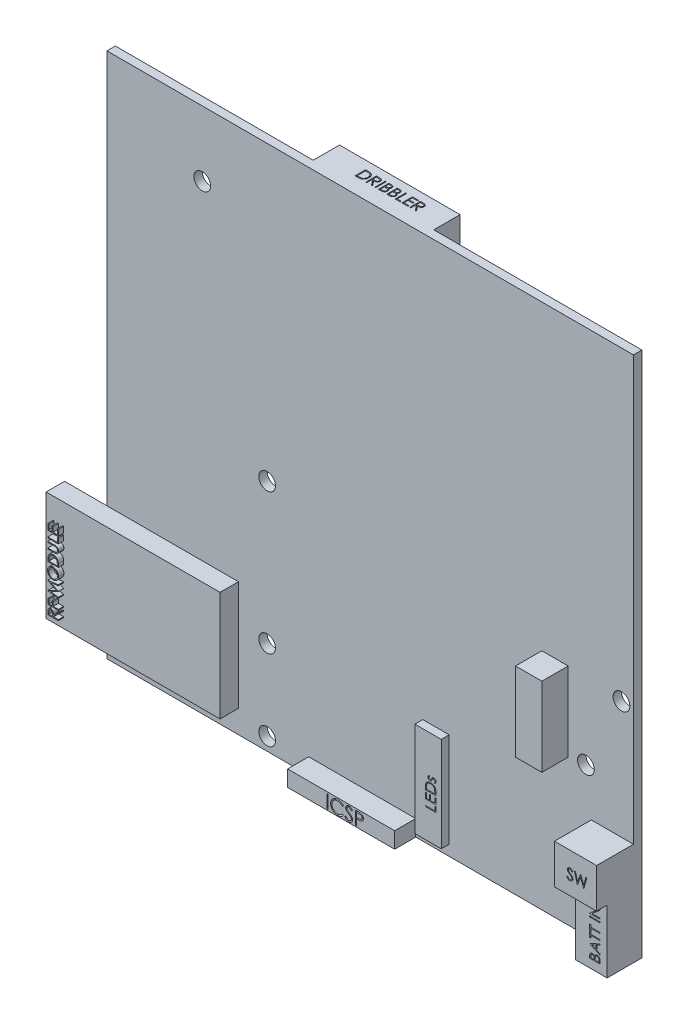
SolidWorks part; units mm, degrees
ref_plane "Front Plane" through (0, 0, 0) normal (0, 0, 1) x (1, 0, 0)
ref_plane "Top Plane" through (0, 0, 0) normal (0, 1, 0) x (1, 0, 0)
ref_plane "Right Plane" through (0, 0, 0) normal (1, 0, 0) x (0, 0, -1)
sketch "Sketch1" plane through (0, 0, 0) normal (0, 0, 1) x (1, 0, 0)
  line L1 (-25.0277, 9.5656) -> (74.9723, 9.5656)
  line L2 (-25.0277, 9.5656) -> (-25.0277, -90.4344)
  line L3 (-25.0277, -90.4344) -> (74.9723, -90.4344)
  line L4 (74.9723, 9.5656) -> (74.9723, -90.4344)
  dimension "D1" = 100
  dimension "D2" = 100
extrude "Boss-Extrude1" add sketch "Sketch1" along normal blind 1.6
sketch "Sketch2" plane through (0, 0, 1.6) normal (0, 0, 1) x (1, 0, 0)
  line L0 (-25.0277, -90.4344) -> (74.9723, -90.4344) construction
  line L1 (-33.0777, -65.2594) -> (-0.0527, -65.2594)
  line L2 (-33.0777, -65.2594) -> (-33.0777, -86.0844)
  line L3 (-33.0777, -86.0844) -> (-0.0527, -86.0844)
  line L4 (-0.0527, -65.2594) -> (-0.0527, -86.0844)
  line L6 (-25.0277, 9.5656) -> (-25.0277, -90.4344) construction
  dimension "D1" = 33.025
  dimension "D2" = 20.825
  dimension "D3" = 4.35
  dimension "D4" = 8.05
extrude "Boss-Extrude2" add sketch "Sketch2" along normal blind 3.5
sketch "Sketch3" plane through (0, 0, 0) normal (0, 0, -1) x (-1, 0, 0)
  line L0 (25.0277, 9.5656) -> (25.0277, -90.4344) construction
  line L1 (-39.4463, -37.1604) -> (-7.4463, -37.1604)
  line L2 (-39.4463, -37.1604) -> (-39.4463, -43.1604)
  line L3 (-39.4463, -43.1604) -> (-7.4463, -43.1604)
  line L4 (-7.4463, -37.1604) -> (-7.4463, -43.1604)
  line L5 (-74.9723, 9.5656) -> (25.0277, 9.5656) construction
  dimension "D1" = 32
  dimension "D2" = 6
  dimension "D3" = 32.474
  dimension "D4" = 46.726
extrude "Boss-Extrude3" add sketch "Sketch3" along normal blind 5
sketch "Sketch4" plane through (0, 0, 1.6) normal (0, 0, 1) x (1, 0, 0)
  line L0 (-25.0277, -86.0844) -> (-25.0277, -90.4344) construction
  line L1 (13.2963, -87.3844) -> (33.6213, -87.3844)
  line L2 (13.2963, -87.3844) -> (13.2963, -90.4344)
  line L3 (13.2963, -90.4344) -> (33.6213, -90.4344)
  line L4 (33.6213, -87.3844) -> (33.6213, -90.4344)
  line L5 (-25.0277, -90.4344) -> (74.9723, -90.4344) construction
  dimension "D1" = 3.05
  dimension "D2" = 38.324
  dimension "D3" = 20.325
extrude "Boss-Extrude4" add sketch "Sketch4" along normal blind 4
sketch "Sketch5" plane through (0, 0, 1.6) normal (0, 0, 1) x (1, 0, 0)
  line L0 (74.9723, -90.4344) -> (74.9723, 9.5656) construction
  line L1 (68.9723, -78.4344) -> (74.9723, -78.4344)
  line L2 (68.9723, -78.4344) -> (68.9723, -90.4344)
  line L3 (68.9723, -90.4344) -> (74.9723, -90.4344)
  line L4 (74.9723, -78.4344) -> (74.9723, -90.4344)
  line L5 (33.6213, -90.4344) -> (74.9723, -90.4344) construction
  dimension "D1" = 6
  dimension "D2" = 12
extrude "Boss-Extrude5" add sketch "Sketch5" along normal blind 5
sketch "Sketch6" plane through (0, 0, 6.6) normal (0, 0, 1) x (1, 0, 0)
  line L0 (73.6619, -89.0757) -> (73.6619, -81.0753) construction
  text T0 "BATT IN" font "Century Gothic" height 2
extrude "Cut-Extrude1" cut sketch "Sketch6" against normal blind 1
sketch "Sketch7" plane through (0, 0, 5.1) normal (0, 0, 1) x (1, 0, 0)
  line L0 (-29.7567, -84.5425) -> (-29.7567, -66.8173) construction
  text T0 "RF MODULE" font "Century Gothic" height 2
extrude "Boss-Extrude6" add sketch "Sketch7" along normal blind 1
sketch "Sketch8" plane through (0, 0, 5.6) normal (0, 0, 1) x (1, 0, 0)
  text T0 "ICSP" font "Century Gothic" height 2.5
extrude "Cut-Extrude2" cut sketch "Sketch8" against normal blind 1
sketch "Sketch9" plane through (0, 0, 1.6) normal (0, 0, 1) x (1, 0, 0)
  line L0 (74.9723, -78.4344) -> (74.9723, 9.5656) construction
  line L1 (57.5723, -47.8094) -> (62.5723, -47.8094)
  line L2 (57.5723, -47.8094) -> (57.5723, -62.8094)
  line L3 (57.5723, -62.8094) -> (62.5723, -62.8094)
  line L4 (62.5723, -47.8094) -> (62.5723, -62.8094)
  line L5 (33.6213, -90.4344) -> (68.9723, -90.4344) construction
  dimension "D1" = 15
  dimension "D2" = 5
  dimension "D3" = 12.4
  dimension "D4" = 27.625
extrude "Boss-Extrude7" add sketch "Sketch9" along normal blind 5
sketch "Sketch11" plane through (0, 0, 0) normal (0, 0, -1) x (-1, 0, 0)
  line L0 (25.0277, 9.5656) -> (25.0277, -90.4344) construction
  line L1 (-35.4463, 9.5656) -> (-12.5463, 9.5656)
  line L2 (-35.4463, 9.5656) -> (-35.4463, 3.0656)
  line L3 (-35.4463, 3.0656) -> (-12.5463, 3.0656)
  line L4 (-12.5463, 9.5656) -> (-12.5463, 3.0656)
  line L5 (-74.9723, 9.5656) -> (25.0277, 9.5656) construction
  dimension "D1" = 37.574
  dimension "D2" = 6.5
  dimension "D3" = 22.9
extrude "Boss-Extrude8" add sketch "Sketch11" along normal blind 5
sketch "Sketch12" plane through (0, 9.5656, 0) normal (0, 1, 0) x (1, 0, 0)
  text T0 "DRIBBLER" font "Century Gothic" height 2
extrude "Cut-Extrude3" cut sketch "Sketch12" against normal blind 1
sketch "Sketch13" plane through (0, 0, 1.6) normal (0, 0, 1) x (1, 0, 0)
  line L0 (-25.0277, 9.5656) -> (-25.0277, -65.2594) construction
  line L1 (74.9723, 9.5656) -> (-25.0277, 9.5656) construction
  circle A0 centre (-6.9277, -2.8344) radius 1.5875
  circle A1 centre (72.6963, -48.5594) radius 1.5875
  circle A2 centre (5.3923, -46.0044) radius 1.5875
  circle A3 centre (5.3923, -72.6844) radius 1.5875
  circle A4 centre (5.3923, -87.9344) radius 1.5875
  circle A5 centre (65.9473, -62.3844) radius 1.5875
  dimension "D1" = 3.175
  dimension "D2" = 3.175
  dimension "D3" = 3.175
  dimension "D4" = 3.175
  dimension "D5" = 3.175
  dimension "D6" = 3.175
  dimension "D7" = 18.1
  dimension "D8" = 12.4
  dimension "D9" = 30.42
  dimension "D10" = 55.57
  dimension "D11" = 30.42
  dimension "D12" = 30.42
  dimension "D13" = 82.25
  dimension "D14" = 97.5
  dimension "D15" = 90.975
  dimension "D16" = 71.95
  dimension "D17" = 97.724
  dimension "D18" = 58.125
extrude "Cut-Extrude5" cut sketch "Sketch13" against normal through all
sketch "Sketch14" plane through (0, 0, 1.6) normal (0, 0, 1) x (1, 0, 0)
  line L0 (-25.0277, 9.5656) -> (-25.0277, -65.2594) construction
  line L1 (34.9723, -70.4344) -> (39.9723, -70.4344)
  line L2 (34.9723, -70.4344) -> (34.9723, -88.4344)
  line L3 (34.9723, -88.4344) -> (39.9723, -88.4344)
  line L4 (39.9723, -70.4344) -> (39.9723, -88.4344)
  line L5 (74.9723, 9.5656) -> (-25.0277, 9.5656) construction
  dimension "D1" = 60
  dimension "D2" = 80
  dimension "D3" = 5
  dimension "D4" = 18
extrude "Boss-Extrude9" add sketch "Sketch14" along normal blind 1.5
sketch "Sketch15" plane through (0, 0, 3.1) normal (0, 0, 1) x (1, 0, 0)
  line L0 (38.9424, -83.2391) -> (38.9424, -73.3783) construction
  text T0 "LEDs" font "Century Gothic" height 2
extrude "Cut-Extrude6" cut sketch "Sketch15" against normal blind 1
sketch "Sketch16" plane through (0, 0, 1.6) normal (0, 0, 1) x (1, 0, 0)
  line L0 (33.6213, -90.4344) -> (68.9723, -90.4344) construction
  line L1 (66.9723, -70.9344) -> (74.9723, -70.9344)
  line L2 (66.9723, -70.9344) -> (66.9723, -78.4344)
  line L3 (66.9723, -78.4344) -> (74.9723, -78.4344)
  line L4 (74.9723, -70.9344) -> (74.9723, -78.4344)
  line L5 (74.9723, -78.4344) -> (74.9723, 9.5656) construction
  dimension "D1" = 8
  dimension "D2" = 7.5
  dimension "D3" = 12
extrude "Boss-Extrude11" add sketch "Sketch16" along normal blind 7
sketch "Sketch17" plane through (0, 0, 8.6) normal (0, 0, 1) x (1, 0, 0)
  text T0 "SW" font "Century Gothic" height 2
extrude "Cut-Extrude7" cut sketch "Sketch17" against normal blind 1
